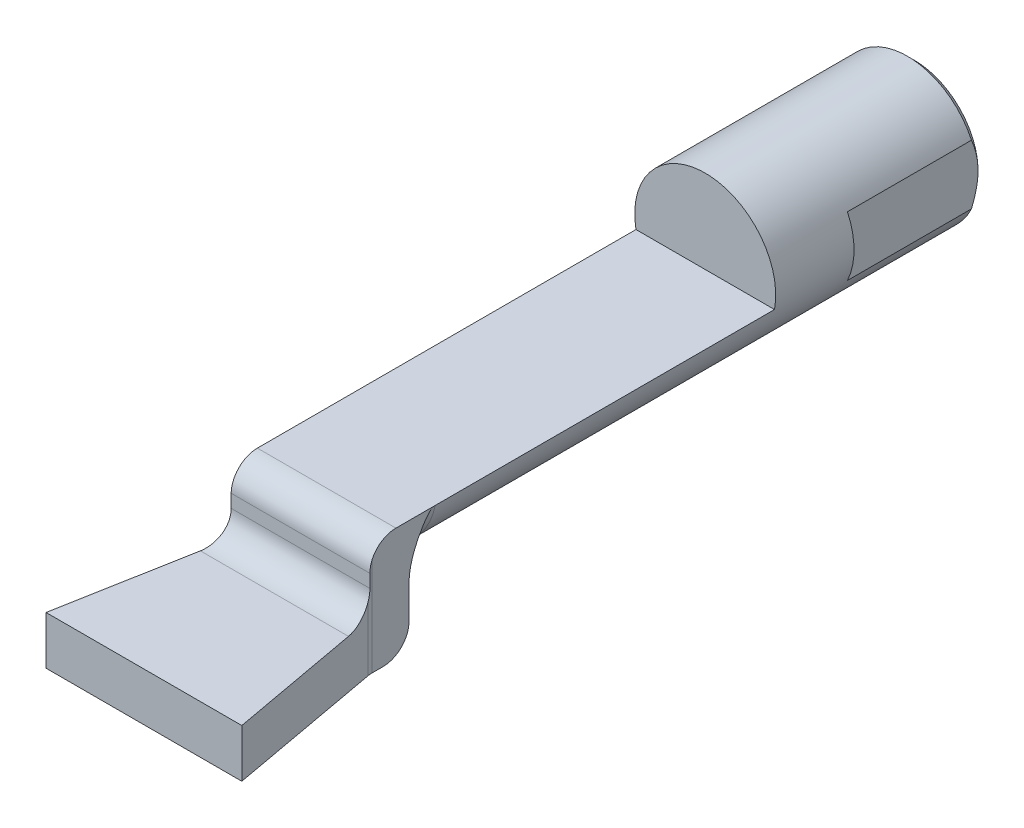
SolidWorks part; units mm, degrees
ref_plane "前视基准面" through (0, 0, 0) normal (0, 0, 1) x (1, 0, 0)
ref_plane "上视基准面" through (0, 0, 0) normal (0, 1, 0) x (1, 0, 0)
ref_plane "右视基准面" through (0, 0, 0) normal (1, 0, 0) x (0, 0, -1)
sketch "草图1" plane through (0, 0, 0) normal (0, 0, 1) x (1, 0, 0)
  circle A0 centre (0, 0) radius 5.4
  dimension "D1" = 10.8
extrude "凸台-拉伸1" add sketch "草图1" along normal blind 44
sketch "草图2" plane through (0, 0, 44) normal (0, 0, 1) x (1, 0, 0)
  line L0 (-5.3066, -1) -> (5.3066, -1)
  arc A0 (5.3066, -1) -> (-5.3066, -1) centre (0, 0) ccw
  circle A1 centre (0, 0) radius 5.4 construction
  dimension "D1" = 1
extrude "切除-拉伸1" cut sketch "草图2" against normal blind 28
sketch "草图3" plane through (0, 0, 44) normal (0, 0, 1) x (1, 0, 0)
  circle A0 centre (-3, -2.5) radius 1
  circle A1 centre (3, -2.5) radius 1
  dimension "D1" = 2
  dimension "D2" = 6
  dimension "D3" = 3
  dimension "D4" = 2.5
extrude "切除-拉伸2" [suppressed] cut sketch "草图3" against normal blind 10
sketch "草图4" plane through (0, 0, 0) normal (0, 0, -1) x (-1, 0, 0)
  line L1 (-5.8955, -2.7209) -> (-4.8955, -2.7209)
  line L2 (-5.8955, -2.7209) -> (-5.8955, 2.2791)
  line L3 (-5.8955, 2.2791) -> (-4.8955, 2.2791)
  line L4 (-4.8955, -2.7209) -> (-4.8955, 2.2791)
  line L5 (-5.8955, -2.7209) -> (-4.8955, 2.2791) construction
  line L6 (-5.8955, 2.2791) -> (-4.8955, -2.7209) construction
  circle A0 centre (0, 0) radius 5.4 construction
  point P0 (-5.3955, -0.2209)
  dimension "D1" = 1
  dimension "D2" = 5
extrude "切除-拉伸3" cut sketch "草图4" against normal blind 10
mirror "镜向1" about plane through (0, 0, 0) normal (1, 0, 0) of "切除-拉伸3"
hole_wizard "M8x1.0 螺纹孔1" positions "草图6" profile "草图5" tap size "M8x1.0" standard "GB"
sketch "草图6" plane through (0, 0, 0) normal (0, 0, -1) x (-1, 0, 0)
  point P0 (0, 0)
sketch "草图5" plane through (0, 0, 0) normal (1, 0, 0) x (0, 1, 0)
  line L0 (0, 0) -> (0, 15.103)
  line L1 (0, 15.103) -> (3.5, 13)
  line L2 (3.5, 13) -> (3.5, 0)
  line L5 (3.5, 0) -> (0, 0)
  line L10 (0, 15.103) -> (-3.5, 13) construction
  line L11 (0, -6.35) -> (0, 107.95) construction
  dimension "螺纹孔钻头直径" = 7
  dimension "螺纹孔钻头深度" = 13
  dimension "导头角度" = 118
cosmetic thread "孔螺蚊线1" parameters "D1"=10, "D2"=8
chamfer "倒角1" distance 0.5 angle 45 3 edges at (-3.5, 0, 0) (0, -5.4, 0) (0, 5.4, 0)
chamfer "倒角2" [suppressed] distance 0.2 angle 45
sketch "草图7" plane through (0, 0, 44) normal (0, 0, 1) x (1, 0, 0)
  line L0 (-5.3066, -1) -> (-5.3066, -10)
  line L1 (-5.3066, -1) -> (5.3066, -1)
  line L2 (5.3066, -1) -> (5.3066, -10)
  line L3 (-5.3066, -10) -> (5.3066, -10)
  point P5 (0, -10)
  point P7 (0, -1)
  dimension "D2" = 10
  dimension "D3" = 10.6132
extrude "凸台-拉伸2" add sketch "草图7" along normal blind 3
sketch "草图9" plane through (0, -10, 0) normal (0, -1, 0) x (1, 0, 0)
  line L0 (5.3066, 47) -> (-5.3066, 47)
  line L1 (-5.3066, 47) -> (-7.5, 59)
  line L2 (-7.5, 59) -> (7.5, 59)
  line L3 (7.5, 59) -> (5.3066, 47)
  point P5 (0, 47)
  point P7 (0, 59)
  dimension "D1" = 12
  dimension "D2" = 15
extrude "凸台-拉伸4" add sketch "草图9" against normal blind 4
fillet "圆角1" radius 2 3 edges at (0, -5.4, 44) (0, -1, 47) (0, -6, 47)
fillet "圆角2" radius 2 2 edges at (-5.3066, -7, 47) (5.3066, -7, 47)
sketch "草图10" plane through (0, -10, 0) normal (0, -1, 0) x (1, 0, 0)
  line L1 (11.663, 59.5107) -> (-11.1698, 59.5107)
  line L2 (11.663, 59.5107) -> (11.663, 42.1396)
  line L3 (11.663, 42.1396) -> (-11.1698, 42.1396)
  line L4 (-11.1698, 59.5107) -> (-11.1698, 42.1396)
extrude "切除-拉伸4" cut sketch "草图10" against normal blind 0.3
fillet "圆角3" radius 2 1 edges at (0, -9.7, 44)
